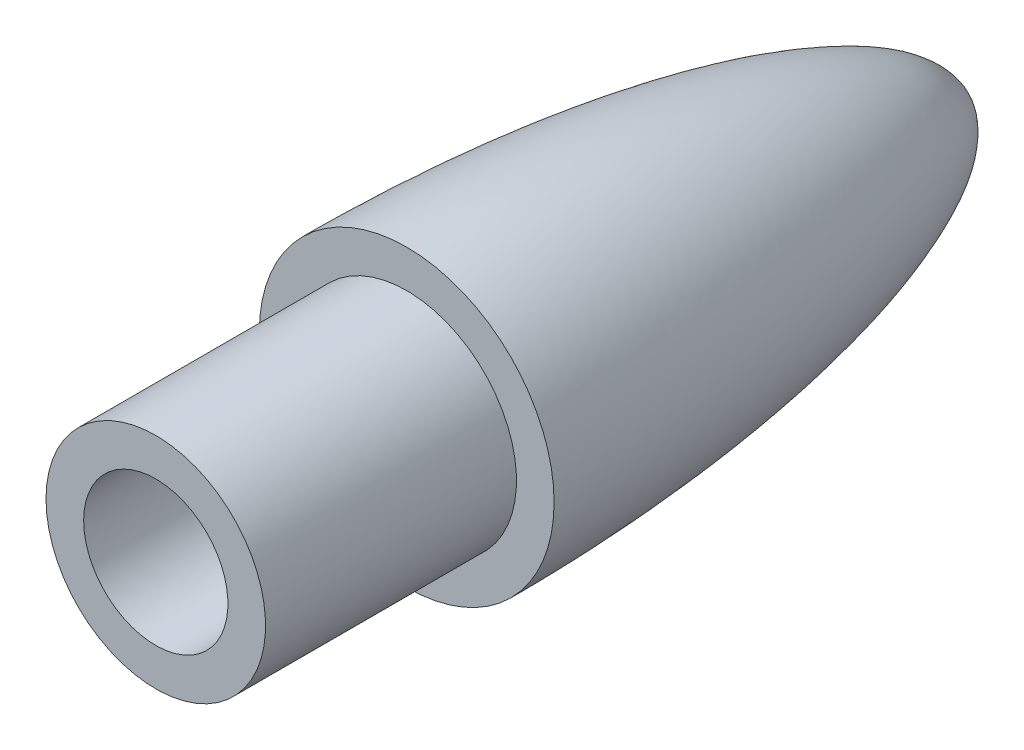
SolidWorks part; units mm, degrees
ref_plane "Front Plane" through (0, 0, 0) normal (0, 0, 1) x (1, 0, 0)
ref_plane "Top Plane" through (0, 0, 0) normal (0, 1, 0) x (1, 0, 0)
ref_plane "Right Plane" through (0, 0, 0) normal (1, 0, 0) x (0, 0, -1)
sketch "Sketch1" plane through (0, 0, 0) normal (0, 1, 0) x (1, 0, 0)
  line L0 (0, 11.4224) -> (0, 8.9224)
  line L4 (-11.75, -32.5776) -> (-8.75, -32.5776)
  line L5 (-8.75, -32.5776) -> (-8.75, -52.5776)
  line L6 (-8.75, -52.5776) -> (-5.75, -52.5776)
  line L7 (-5.75, -52.5776) -> (-5.75, -29.5776)
  line L8 (-5.75, -29.5776) -> (-8.75, -29.5776)
  line L12 (0, 8.9224) -> (-6.0343, -1.9436)
  line L13 (-6.0343, -1.9436) -> (-8.75, -29.5776)
  spline S0 degree 3 poles (0, 11.4224) (-1.2784, 11.417) (-3.8731, 9.5587) (-5.9448, 5.6272) (-7.7109, 0.9059) (-8.8856, -3.5703) (-9.8914, -8.5946) (-10.6705, -13.7918) (-11.219, -19.122) (-11.5302, -23.7907) (-11.7075, -28.0933) (-11.75, -30.9224) (-11.75, -32.5776) knots 0 0 0 0 0.077096 0.191083 0.276022 0.396034 0.482753 0.599803 0.727919 0.821235 0.895417 1 1 1 1
  dimension "D2" = 8.75
  dimension "D1" = 2.5
  dimension "D3" = 44
  dimension "D5" = 3
  dimension "D6" = 20
  dimension "D7" = 3
  dimension "D8" = 23
revolve "Revolve1" add sketch "Sketch1" angle 360 about L0
